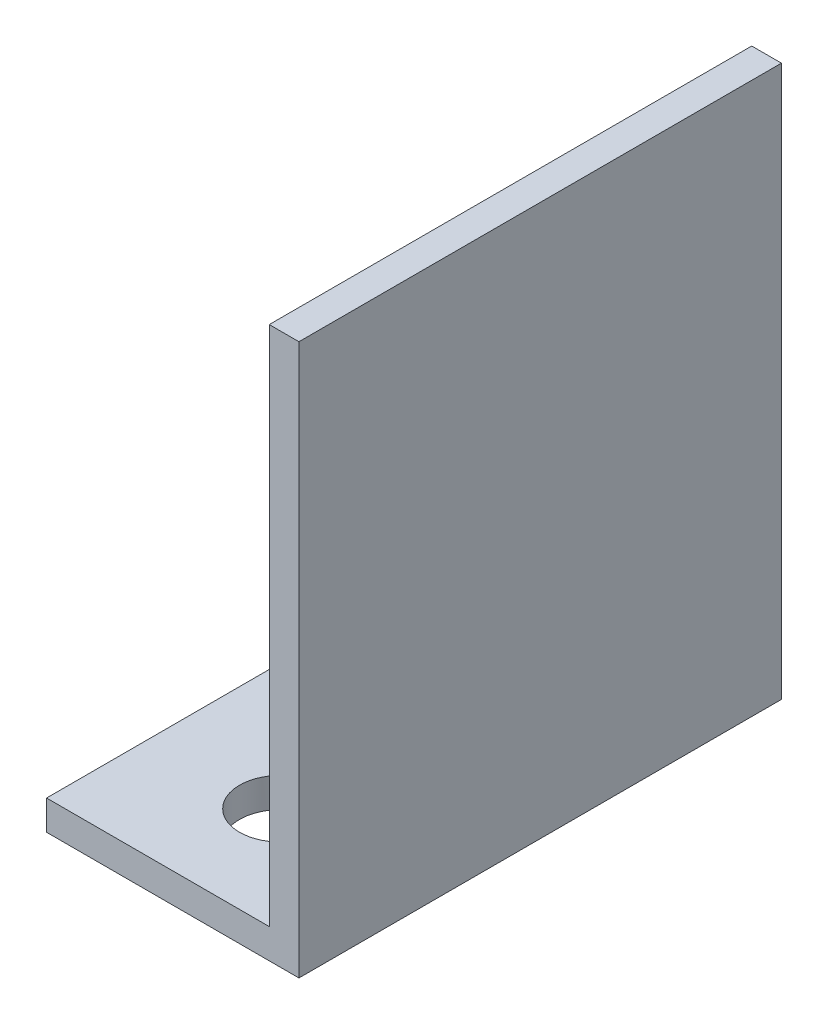
SolidWorks part; units mm, degrees
ref_plane "Front Plane" through (0, 0, 0) normal (1, 0, 0) x (0, 1, 0)
ref_plane "Top Plane" through (0, 0, 0) normal (0, 0, 1) x (0, 1, 0)
ref_plane "Right Plane" through (0, 0, 0) normal (0, 1, 0) x (-1, 0, 0)
sketch "Sketch1" plane through (0, 0, 0) normal (0, 0, 1) x (0, 1, 0)
  line L0 (0, 0) -> (0, -15)
  line L1 (0, -15) -> (35.1185, -15)
  line L2 (35.1185, -15) -> (35.1185, -17)
  line L3 (35.1185, -17) -> (-2, -17)
  line L4 (-2, -17) -> (-2, 0)
  line L5 (-2, 0) -> (0, 0)
  dimension "D1" = 15
  dimension "D2" = 2
extrude "Boss-Extrude1" add sketch "Sketch1" along normal blind 32.5
sketch "Sketch2" plane through (0, -2, 0) normal (0, -1, 0) x (1, 0, 0)
  line L0 (0, 16.25) -> (17, 16.25) construction
  line L1 (0, 32.5) -> (0, 0) construction
  line L2 (17, 32.5) -> (17, 0) construction
  line L3 (8.5, 32.5) -> (8.5, 0) construction
  line L4 (0, 32.5) -> (17, 32.5) construction
  line L5 (0, 0) -> (17, 0) construction
  circle A0 centre (8.5, 25.25) radius 2.75
  circle A1 centre (8.5, 7.25) radius 2.75
  point P10 (0, 0)
  point P11 (0, 0)
  dimension "D1" = 5.5
  dimension "D2" = 18
extrude "Cut-Extrude1" cut sketch "Sketch2" against normal up to surface (2 mm away) up to face at (7.5, 0, 16.25)
